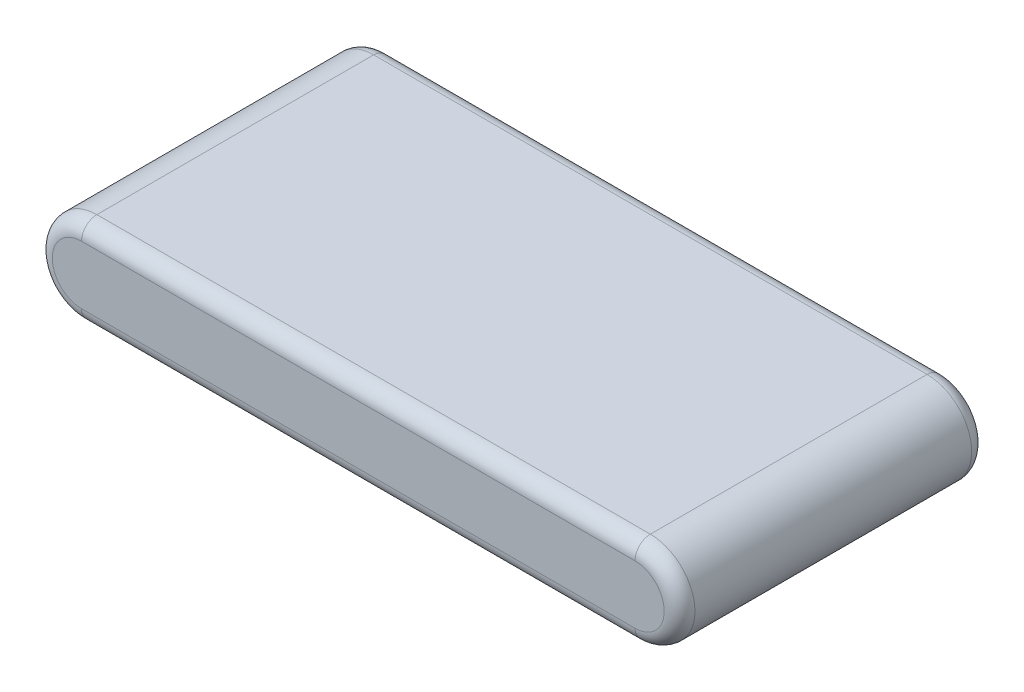
SolidWorks part; units mm, degrees
ref_plane "Plano frontal" through (0, 0, 0) normal (0, 0, 1) x (1, 0, 0)
ref_plane "Plano superior" through (0, 0, 0) normal (0, 1, 0) x (1, 0, 0)
ref_plane "Plano direito" through (0, 0, 0) normal (1, 0, 0) x (0, 0, -1)
sketch "Esboço1" plane through (0, 0, 0) normal (0, 0, 1) x (1, 0, 0)
  line L2 (9, 1.45) -> (-9, 1.45)
  line L3 (-9, -1.45) -> (9, -1.45)
  arc A2 (-9, 1.45) -> (-9, -1.45) centre (-9, 0) ccw
  arc A3 (9, -1.45) -> (9, 1.45) centre (9, 0) ccw
extrude "Ressalto-extrusão1" add sketch "Esboço1" along normal blind 10
fillet "Filete1" radius 0.5 8 edges at (0, 1.45, 0) (-10.45, 0, 0) (0, -1.45, 0) (10.45, 0, 0) (0, -1.45, 10) (-10.45, 0, 10) (0, 1.45, 10) (10.45, 0, 10)
sketch "Esboço2" plane through (0, 0, 10) normal (0, 0, 1) x (1, 0, 0)
  line L0 (-10.45, 0) -> (10.45, 0) construction
  line L2 (-9, 1.45) -> (9, 1.45) construction
  line L3 (0, 1.45) -> (0, -1.45) construction
  line L4 (9, -1.45) -> (-9, -1.45) construction
  arc A0 (-9, 1.45) -> (-9, -1.45) centre (-9, 0) ccw construction
  arc A1 (9, -1.45) -> (9, 1.45) centre (9, 0) ccw construction
